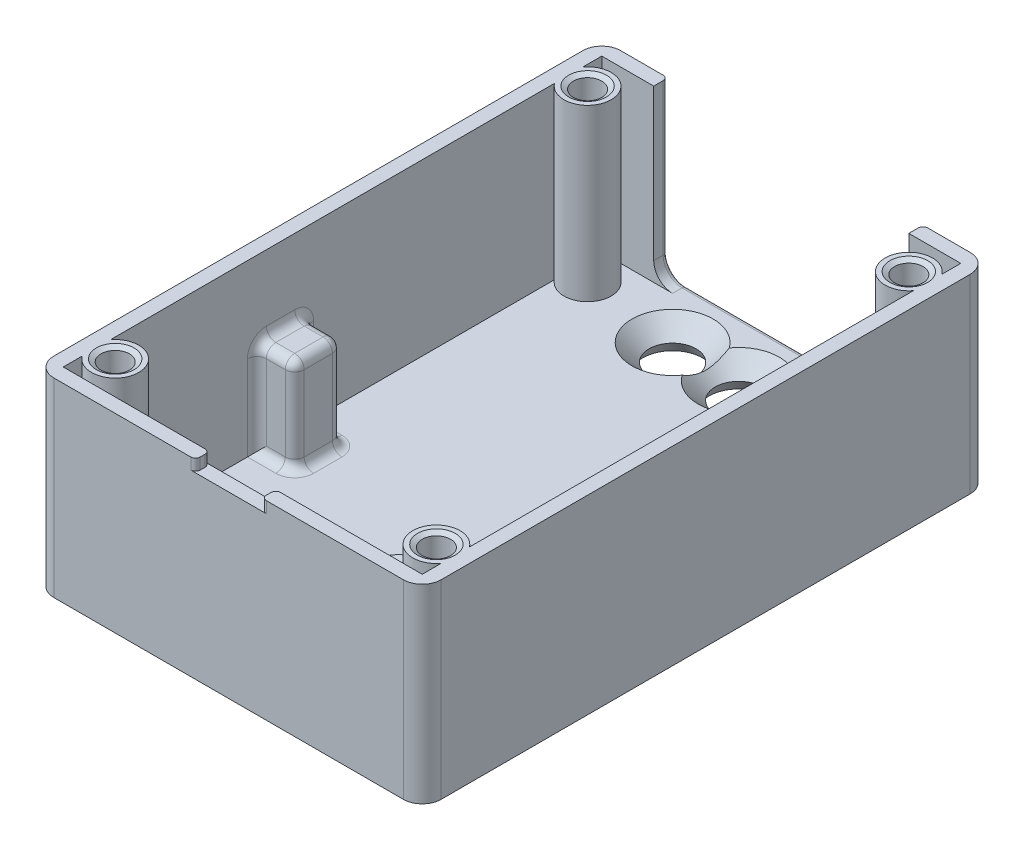
SolidWorks part; units mm, degrees
ref_plane "Спереди" through (0, 0, 0) normal (0, 0, 1) x (1, 0, 0)
ref_plane "Сверху" through (0, 0, 0) normal (0, 1, 0) x (1, 0, 0)
ref_plane "Справа" through (0, 0, 0) normal (1, 0, 0) x (0, 0, -1)
sketch "Эскиз1" plane through (0, 0, 0) normal (0, 1, 0) x (1, 0, 0)
  line L0 (-3.5, 45.8352) -> (-3.5, -34.761) construction
  line L1 (-20.5, -30) -> (20.5, -30)
  line L2 (-20.5, -30) -> (-20.5, 30)
  line L3 (-20.5, 30) -> (20.5, 30)
  line L4 (20.5, -30) -> (20.5, 30)
  line L5 (0, 30) -> (0, -30) construction
  line L6 (-20.5, 0) -> (20.5, 0) construction
  circle A0 centre (0, 24) radius 2.3
  circle A1 centre (0, -24) radius 2.3
  circle A2 centre (0, -12) radius 1.9
  circle A5 centre (-7, -24) radius 2.3
  circle A6 centre (-7, 24) radius 2.3
  point P0 (0, 0)
  dimension "D1" = 48
  dimension "D2" = 4.6
  dimension "D4" = 6
  dimension "D7" = 3.8
  dimension "D3" = 60
  dimension "D5" = 41
  dimension "D6" = 12
  dimension "D8" = 3.5
extrude "Бобышка-Вытянуть1" add sketch "Эскиз1" along normal blind 3
chamfer "Фаска1" distance 2 angle 45 4 edges at (0, 3, 26.3) (0, 3, -21.7) (-7, 3, 21.7) (-7, 3, -26.3)
sketch "Эскиз2" plane through (0, 3, 0) normal (0, 1, 0) x (1, 0, 0)
  line L0 (-20.5, 30) -> (20.5, 30)
  line L2 (-20.5, 30) -> (-20.5, -30)
  line L3 (-20.5, -30) -> (20.5, -30)
  line L4 (20.5, 30) -> (20.5, -30)
extrude "Вытянуть-Тонкостенный1" add sketch "Эскиз2" along normal blind 18 thin
sketch "Эскиз3" plane through (0, 21, 0) normal (0, 1, 0) x (1, 0, 0)
  line L0 (0, 32.0771) -> (0, 0) construction
  line L2 (-13.5, 27.9629) -> (13.5, 27.9629)
  line L3 (-13.5, 27.9629) -> (-13.5, 30.9933)
  line L4 (-13.5, 30.9933) -> (13.5, 30.9933)
  line L5 (13.5, 27.9629) -> (13.5, 30.9933)
  line L6 (0, 30.9933) -> (0, 27.9629) construction
  line L7 (-13.5, 29.4781) -> (13.5, 29.4781) construction
  point P3 (0, 29.4781)
  dimension "D1" = 27
extrude "Вырез-Вытянуть1" cut sketch "Эскиз3" against normal up to surface (18 mm away) up to face at (0, 3, 0)
sketch "Эскиз4" plane through (0, 3, 0) normal (0, 1, 0) x (1, 0, 0)
  line L0 (0, 32.478) -> (0, 0) construction
  line L1 (0, 0) -> (39.8357, 0) construction
  line L3 (20.5, -30) -> (20.5, 30) construction
  circle A0 centre (17, 25) radius 2.5
  circle A1 centre (-17, 25) radius 2.5
  circle A2 centre (17, -25) radius 2.5
  circle A3 centre (-17, -25) radius 2.5
  dimension "D1" = 5
  dimension "D3" = 3.5
  dimension "D4" = 50
  dimension "D2" = 25
extrude "Бобышка-Вытянуть2" add sketch "Эскиз4" along normal up to surface (18 mm away) up to face at (0, 21, -9.75)
sketch "Эскиз5" plane through (0, 21, 0) normal (0, 1, 0) x (1, 0, 0)
  line L0 (20.5, -30) -> (20.5, 30) construction
  circle A0 centre (17, 25) radius 1.5
  circle A1 centre (17, -25) radius 1.5
  circle A2 centre (-17, -25) radius 1.5
  circle A3 centre (-17, 25) radius 1.5
  dimension "D1" = 3
  dimension "D2" = 3.5
extrude "Вырез-Вытянуть2" cut sketch "Эскиз5" against normal blind 10
sketch "Эскиз7" plane through (0, 21, 0) normal (0, 1, 0) x (1, 0, 0)
  line L1 (-3.5, -30.9828) -> (3.5, -30.9828)
  line L2 (-3.5, -30.9828) -> (-3.5, -26.6268)
  line L3 (-3.5, -26.6268) -> (3.5, -26.6268)
  line L4 (3.5, -30.9828) -> (3.5, -26.6268)
  line L5 (0, -26.6268) -> (0, -30.9828) construction
  line L6 (-3.5, -28.8048) -> (3.5, -28.8048) construction
  point P0 (0, -28.8048)
  dimension "D1" = 7
extrude "Вырез-Вытянуть3" cut sketch "Эскиз7" against normal blind 1.2
fillet "Скругление2" radius 0.5 4 edges at (-3.5, 20.4, 28.5) (-3.5, 20.4, 30) (3.5, 20.4, 30) (3.5, 20.4, 28.5)
fillet "Скругление3" radius 2 4 edges at (20.5, 10.5, -30) (-20.5, 10.5, -30) (-20.5, 10.5, 30) (20.5, 10.5, 30)
chamfer "Фаска4" distance 1.5 angle 30 13 edges at (0, 0, 26.3) (0, 0, -30) (-20.5, 0, 0) (0, 0, 30) (20.5, 0, 0) (0, 0, -21.7) (-19.9142, 0, -29.4142) (-19.9142, 0, 29.4142) (19.9142, 0, 29.4142) (19.9142, 0, -29.4142) (0, 0, 13.9) (-7, 0, -26.3) (-7, 0, 21.7)
chamfer "Фаска6" distance 0.5 angle 30 4 edges at (-17, 21, -23.5) (-17, 21, 26.5) (17, 21, 26.5) (17, 21, -23.5)
sketch "Эскиз8" plane through (0, 3, 0) normal (0, 1, 0) x (1, 0, 0)
  line L0 (-24.1981, 0) -> (27.887, 0) construction
  line L1 (19, -23.5) -> (19, 23.5) construction
  line L2 (19, -11.5) -> (15, -11.5)
  line L3 (19, -11.5) -> (19, -16.5)
  line L4 (19, -16.5) -> (15, -16.5)
  line L5 (15, -11.5) -> (15, -16.5)
  line L6 (-19, 23.5) -> (-19, -23.5) construction
  line L7 (-19, -3) -> (-15, -3)
  line L8 (-19, -3) -> (-19, -8)
  line L9 (-19, -8) -> (-15, -8)
  line L10 (-15, -3) -> (-15, -8)
  dimension "D1" = 11.5
  dimension "D2" = 4
  dimension "D3" = 5
  dimension "D4" = 3
  dimension "D5" = 5
  dimension "D6" = 4
extrude "Бобышка-Вытянуть3" add sketch "Эскиз8" along normal blind 10
fillet "Скругление6" radius 1 22 edges at (-17, 3, 8) (-17, 3, 3) (-19, 8, 3) (-19, 8, 8) (17, 3, 11.5) (17, 3, 16.5) (-15, 8, 8) (-15, 8, 3) (-15, 3, 5.5) (-17, 13, 3) (-15, 13, 5.5) (-17, 13, 8) (-19, 13, 5.5) (17, 13, 16.5) (17, 13, 11.5) (19, 13, 14) (15, 8, 11.5) (15, 13, 14) (15, 8, 16.5) (15, 3, 14) (19, 8, 16.5) (19, 8, 11.5)
fillet "Скругление7" radius 2 2 edges at (13.5, 3, -29.25) (-13.5, 3, -29.25)
fillet "Скругление8" radius 0.5 5 edges at (13.5, 13, -30) (12.9142, 3.5858, -30) (0, 3, -30) (-12.9142, 3.5858, -30) (-13.5, 13, -30)
chamfer "Фаска7" distance 1 angle 45 1 edges at (0, 3, 13.9)
